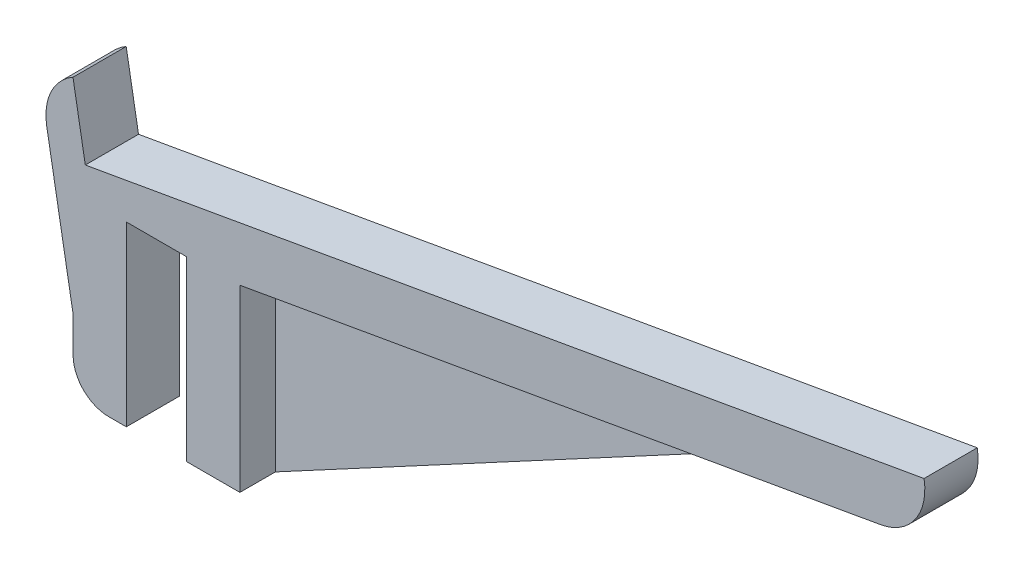
SolidWorks part; units mm, degrees
ref_plane "Front Plane" through (0, 0, 0) normal (0, 0, 1) x (1, 0, 0)
ref_plane "Top Plane" through (0, 0, 0) normal (0, 1, 0) x (1, 0, 0)
ref_plane "Right Plane" through (0, 0, 0) normal (1, 0, 0) x (0, 0, -1)
sketch "Sketch1" plane through (0, 0, 0) normal (0, 0, 1) x (1, 0, 0)
  line L0 (0, 0) -> (0, -50)
  line L1 (0, -50) -> (15, -50)
  line L2 (15, -50) -> (15, 0.5653)
  line L3 (15, 0.5653) -> (210.3922, 35.0182)
  line L4 (0, 0) -> (-17, 0)
  line L5 (-17, 0) -> (-17, -50)
  line L6 (-17, -50) -> (-32, -50)
  line L7 (-32, -50) -> (-32, -30)
  line L8 (-32, -30) -> (-41.8874, 26.0745)
  line L9 (-41.8874, 26.0745) -> (-32.0394, 27.811)
  line L10 (-32.0394, 27.811) -> (-28.5664, 8.1148)
  line L11 (-28.5664, 8.1148) -> (207.7875, 49.7904)
  line L12 (207.7875, 49.7904) -> (210.3922, 35.0182)
  line L13 (-17, -50) -> (0, -50) construction
  dimension "D1" = 17
  dimension "D2" = 15
  dimension "D3" = 15
  dimension "D4" = 15
  dimension "D5" = 10
  dimension "D6" = 240
  dimension "D7" = 50
  dimension "D8" = 20
  dimension "D9" = 10
  dimension "D10" = 20
  dimension "D11" = 10
extrude "Boss-Extrude1" add sketch "Sketch1" along normal blind 15
sketch "Sketch2" plane through (0, 0, 0) normal (0, 0, 1) x (1, 0, 0)
  line L0 (15, -50) -> (154.9065, 25.2346)
  line L1 (15, 0.5653) -> (210.3922, 35.0182) construction
  line L2 (154.9065, 25.2346) -> (15, 0.5653)
  line L3 (15, 0.5653) -> (15, -50)
extrude "Boss-Extrude2" add sketch "Sketch2" along normal blind 5
fillet "Fillet1" radius 15 1 edges at (-41.8874, 26.0745, 7.5)
fillet "Fillet2" radius 10 1 edges at (-32, -50, 7.5)
fillet "Fillet3" radius 15 1 edges at (210.3922, 35.0182, 7.5)
